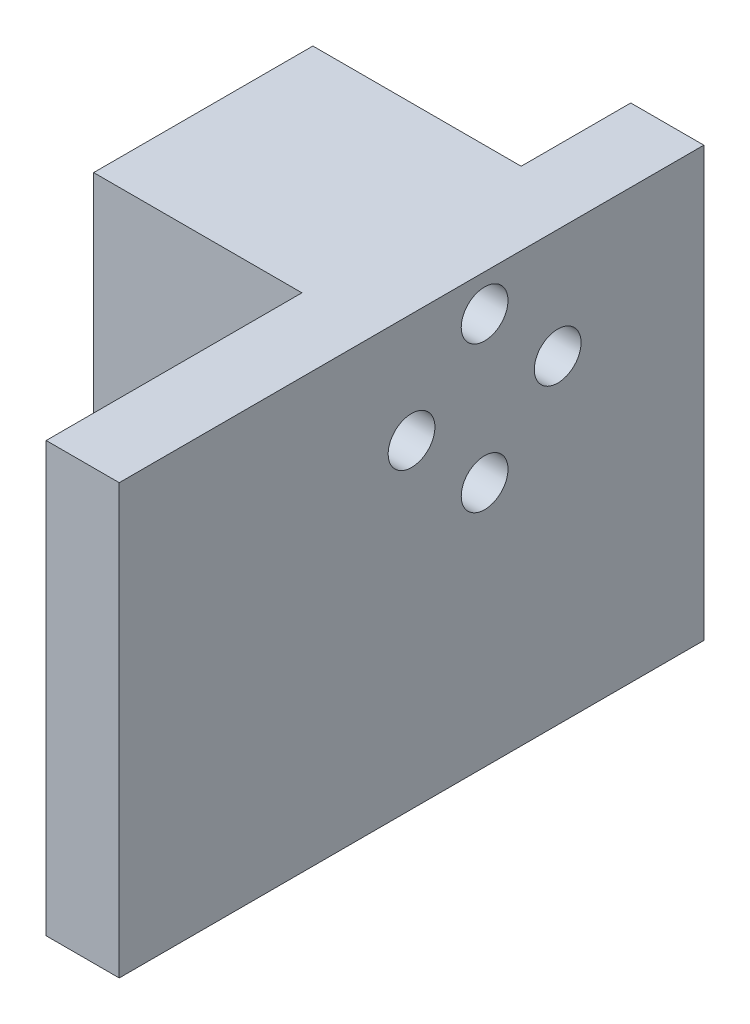
SolidWorks part; units mm, degrees
ref_plane "Front Plane" through (0, 0, 0) normal (0, 0, 1) x (1, 0, 0)
ref_plane "Top Plane" through (0, 0, 0) normal (0, 1, 0) x (1, 0, 0)
ref_plane "Right Plane" through (0, 0, 0) normal (1, 0, 0) x (0, 0, -1)
sketch "Sketch1" plane through (0, 0, 0) normal (0, 1, 0) x (1, 0, 0)
  line L1 (-75, 85) -> (75, 85)
  line L2 (-75, 85) -> (-75, -85)
  line L3 (-75, -85) -> (75, -85)
  line L4 (75, 85) -> (75, -85)
  line L5 (-75, 85) -> (75, -85) construction
  line L6 (-75, -85) -> (75, 85) construction
  line L7 (45, -85) -> (-45, -85)
  line L8 (45, -85) -> (45, -80)
  line L9 (45, -80) -> (-45, -80)
  line L10 (-45, -85) -> (-45, -80)
  line L11 (-18.5, 10) -> (18.5, 10)
  line L12 (-18.5, 10) -> (-18.5, -10)
  line L13 (-18.5, -10) -> (18.5, -10)
  line L14 (18.5, 10) -> (18.5, -10)
  line L15 (-18.5, 10) -> (18.5, -10) construction
  line L16 (-18.5, -10) -> (18.5, 10) construction
  line L17 (45, -85) -> (75, -85)
  line L18 (45, -85) -> (45, -45)
  line L19 (45, -45) -> (75, -45)
  line L20 (75, -85) -> (75, -45)
  line L21 (-45, -85) -> (-75, -85)
  line L22 (-45, -85) -> (-45, -45)
  line L23 (-45, -45) -> (-75, -45)
  line L24 (-75, -85) -> (-75, -45)
  line L25 (75, -25) -> (75, -45)
  line L26 (-7.5, 10) -> (7.5, 10)
  line L27 (45, -45) -> (75, -25)
  line L28 (-45, -45) -> (-75, -25)
  line L29 (-7.5, 10) -> (-7.5, 50)
  line L30 (-7.5, 50) -> (7.5, 50)
  line L31 (7.5, 10) -> (7.5, 50)
  point P0 (0, 0)
  point P10 (0, 0)
  dimension "D1" = 150
  dimension "D2" = 170
  dimension "D3" = 30
  dimension "D4" = 30
  dimension "D5" = 5
  dimension "D6" = 37
  dimension "D7" = 20
  dimension "D8" = 40
  dimension "D9" = 40
  dimension "D10" = 20
  dimension "D11" = 20
  dimension "D12" = 7.5
  dimension "D13" = 7.5
  dimension "D14" = 40
extrude "Boss-Extrude1" add sketch "Sketch1" along normal blind 5 contours L23 L22 L9 L18 L19 L4 L1 L2 L11 L14 L13 L12 region at (0, 0, -82.7701)
sketch "Sketch2" plane through (0, 5, 0) normal (0, 1, 0) x (1, 0, 0)
  line L0 (0, 0) -> (0, -39.6646) construction
sketch "Sketch3" plane through (0, 5, 0) normal (0, 1, 0) x (1, 0, 0)
  line L0 (-18.5, 10) -> (-18.5, -10) construction
  line L1 (-18.5, 10) -> (-7.5, 10) construction
  line L2 (0, 0) -> (0, -17.2633) construction
  circle A0 centre (-35, 20) radius 1.6
  circle A1 centre (-35, -20) radius 1.6
  circle A2 centre (35, -20) radius 1.6
  circle A3 centre (35, 20) radius 1.6
  dimension "D1" = 3.2
  dimension "D2" = 40
  dimension "D3" = 16.5
  dimension "D4" = 10
extrude "Cut-Extrude1" cut sketch "Sketch3" against normal through all and the other way through all
sketch "Sketch4" plane through (0, 5, 0) normal (0, 1, 0) x (1, 0, 0)
  line L0 (-75, 85) -> (75, 85) construction
  line L1 (-75, 85) -> (-70, 85)
  line L2 (-75, 85) -> (-75, -23)
  line L3 (-75, -23) -> (-70, -23)
  line L4 (-70, 85) -> (-70, -23)
  line L5 (-70, -11.5) -> (-75, -11.5)
  line L6 (-70, -11.5) -> (-70, 3.5)
  line L7 (-70, 3.5) -> (-75, 3.5)
  line L8 (-75, -11.5) -> (-75, 3.5)
  line L9 (-70, 23.5) -> (-75, 23.5)
  line L10 (-70, 23.5) -> (-70, 38.5)
  line L11 (-70, 38.5) -> (-75, 38.5)
  line L12 (-75, 23.5) -> (-75, 38.5)
  line L13 (0, 0) -> (0, 26.7337) construction
  line L14 (-70, 3.5) -> (-60, 3.5)
  line L15 (-70, 58.5) -> (-75, 58.5)
  line L16 (-70, 58.5) -> (-70, 73.5)
  line L17 (-70, 73.5) -> (-75, 73.5)
  line L18 (-75, 58.5) -> (-75, 73.5)
  line L19 (-70, 73.5) -> (-60, 73.5)
  line L20 (-70, 73.5) -> (-70, 58.5)
  line L21 (-70, 58.5) -> (-60, 58.5)
  line L22 (-60, 73.5) -> (-60, 58.5)
  line L23 (-70, 3.5) -> (-70, -11.5)
  line L24 (-70, -11.5) -> (-60, -11.5)
  line L25 (-60, 3.5) -> (-60, -11.5)
  circle A0 centre (-65, 66) radius 2.55
  circle A1 centre (-65, -4) radius 2.55
  circle A2 centre (65, 66) radius 2.55
  circle A3 centre (65, -4) radius 2.55
  dimension "D10" = 5.1
  dimension "D12" = 5.1
  dimension "D13" = 7.5
  dimension "D14" = 5
  dimension "D15" = 5
  dimension "D16" = 7.5
  dimension "D1" = 5
  dimension "D2" = 15
  dimension "D3" = 108
  dimension "D4" = 15
  dimension "D5" = 20
  dimension "D6" = 15
  dimension "D7" = 20
  dimension "D8" = 11.5
  dimension "D9" = 10
  dimension "D11" = 10
extrude "Cut-Extrude2" cut sketch "Sketch4" against normal blind 10 contours A0 | A3 | A1 | A2 region at (-65, 5, -66) region at (65, 5, 4)
sketch "Sketch5" plane through (0, 5, 0) normal (0, 1, 0) x (1, 0, 0)
  line L0 (0, 0) -> (0, -51.3371) construction
  line L1 (45, -80) -> (-45, -80) construction
  line L4 (-45, -45) -> (-42, -45)
  line L5 (-45, -45) -> (-45, -80)
  line L6 (-45, -80) -> (-42, -80)
  line L7 (-42, -45) -> (-42, -80)
  line L8 (-42, -70) -> (-36, -70)
  line L9 (-42, -70) -> (-42, -80)
  line L10 (-42, -80) -> (-36, -80)
  line L11 (-36, -70) -> (-36, -80)
  circle A0 centre (-39, -75) radius 1.55
  circle A1 centre (39, -75) radius 1.55
  circle A2 centre (-39, -50) radius 1.55
  circle A3 centre (39, -50) radius 1.55
  dimension "D1" = 3.1
  dimension "D2" = 5
  dimension "D3" = 3
  dimension "D8" = 3.1
  dimension "D9" = 25
  dimension "D10" = 5
  dimension "D4" = 3
  dimension "D5" = 6
  dimension "D6" = 0
  dimension "D7" = 10
extrude "Cut-Extrude3" cut sketch "Sketch5" against normal through all contours A2 | A0 | A1 | A3
sketch "Sketch6" plane through (0, 5, 0) normal (0, 1, 0) x (1, 0, 0)
  line L0 (-75, 85) -> (75, 85) construction
  line L1 (70, 85) -> (55, 85)
  line L2 (70, 85) -> (70, 75)
  line L3 (70, 75) -> (55, 75)
  line L4 (55, 85) -> (55, 75)
  line L5 (75, 85) -> (75, -25) construction
  line L6 (0, 0) -> (0, 22.1653) construction
  line L7 (-55, 85) -> (-55, 75)
  line L8 (-70, 75) -> (-55, 75)
  line L9 (-70, 85) -> (-70, 75)
  line L10 (-70, 85) -> (-55, 85)
  circle A0 centre (62.5, 80) radius 1.55
  circle A1 centre (-62.5, 80) radius 1.55
  dimension "D4" = 3.1
  dimension "D5" = 5
  dimension "D6" = 7.5
  dimension "D1" = 5
  dimension "D2" = 10
  dimension "D3" = 15
extrude "Cut-Extrude4" cut sketch "Sketch6" against normal through all contours A0 | A1 region at (62.5, 5, -80)
sketch "Sketch7" plane through (0, 5, 0) normal (0, 1, 0) x (1, 0, 0)
  line L0 (0, 0) -> (0, 72.5289) construction
  line L1 (-75, 85) -> (-98, 85)
  line L2 (-75, 85) -> (-75, -25)
  line L3 (-75, -25) -> (-98, -25)
  line L4 (-98, 85) -> (-98, -25)
  line L5 (98, 85) -> (98, -25)
  line L6 (75, -25) -> (98, -25)
  line L7 (75, 85) -> (75, -25)
  line L8 (75, 85) -> (98, 85)
  dimension "D1" = 23
extrude "Boss-Extrude2" add sketch "Sketch7" against normal blind 5
sketch "Sketch9" plane through (0, 5, 0) normal (0, 1, 0) x (1, 0, 0)
  line L1 (-44.75, 15) -> (-39.75, 15)
  line L2 (-44.75, 15) -> (-44.75, -25)
  line L3 (-44.75, -25) -> (-39.75, -25)
  line L4 (-39.75, 15) -> (-39.75, -25)
  line L8 (0, 0) -> (0, -58.9253) construction
  line L9 (39.75, 15) -> (39.75, -25)
  line L10 (44.75, -25) -> (39.75, -25)
  line L11 (44.75, 15) -> (44.75, -25)
  line L12 (44.75, 15) -> (39.75, 15)
  line L14 (-98, 85) -> (-98, -25) construction
  dimension "D1" = 53.25
  dimension "D2" = 5
  dimension "D3" = 40
extrude "Boss-Extrude4" add sketch "Sketch9" along normal blind 33
sketch "Sketch11" plane through (0, 5, 0) normal (0, 1, 0) x (1, 0, 0)
  line L0 (-98, 85) -> (-98, -25) construction
  line L1 (-73, 24.3058) -> (-61, 24.3058)
  line L2 (-73, 24.3058) -> (-73, 12.3058)
  line L3 (-73, 12.3058) -> (-61, 12.3058)
  line L4 (-61, 24.3058) -> (-61, 12.3058)
  line L5 (0, 0) -> (0, 34.4815) construction
  line L6 (61, 24.3058) -> (61, 12.3058)
  line L7 (73, 12.3058) -> (61, 12.3058)
  line L8 (73, 24.3058) -> (73, 12.3058)
  line L9 (73, 24.3058) -> (61, 24.3058)
  dimension "D1" = 25
  dimension "D2" = 12
  dimension "D3" = 12
extrude "Cut-Extrude5" cut sketch "Sketch11" against normal blind 50
sketch "Sketch12" plane through (-44.75, 0, 0) normal (-1, 0, 0) x (0, 0, 1)
  line L0 (-15, 38) -> (-15, 5) construction
  line L1 (-7.5, 34.35) -> (7.5, 34.35)
  line L2 (-7.5, 34.35) -> (-7.5, 19.35)
  line L3 (-7.5, 19.35) -> (7.5, 19.35)
  line L4 (7.5, 34.35) -> (7.5, 19.35)
  line L5 (-15, 38) -> (25, 38) construction
  line L6 (0, 34.35) -> (0, 19.35) construction
  line L7 (0, 34.35) -> (0, 26.85) construction
  line L8 (0, 34.35) -> (0, 19.35) construction
  line L9 (0, 19.35) -> (0, 26.85) construction
  line L10 (0, 26.85) -> (7.5, 26.85) construction
  circle A0 centre (0, 31.85) radius 1.6
  circle A4 centre (5, 26.85) radius 1.6
  circle A5 centre (0, 21.85) radius 1.6
  circle A6 centre (-5, 26.85) radius 1.6
  point P23 (-2.6824, 31.0425)
  point P24 (0, 26.85)
  dimension "D5" = 3.2
  dimension "D6" = 5
  dimension "D8" = 0
  dimension "D9" = 5
  dimension "D10" = 5
  dimension "D1" = 7.5
  dimension "D2" = 15
  dimension "D3" = 3.65
  dimension "D4" = 15
  dimension "D7" = 4
extrude "Cut-Extrude6" cut sketch "Sketch12" against normal blind 50 contours A0 | A4 | A6 | A5 region at (-44.75, 31.85, 0) region at (-44.75, 26.85, 5) region at (-44.75, 21.85, 0) region at (-44.75, 26.85, -5)
sketch "Sketch13" plane through (-44.75, 0, 0) normal (-1, 0, 0) x (0, 0, 1)
  line L6 (0, 34.35) -> (0, 19.35) construction
  line L7 (0, 19.35) -> (0, 26.85) construction
  line L8 (0, 26.85) -> (7.5, 26.85) construction
  line L9 (-15, 38) -> (-15, 5) construction
  line L10 (-7.5, 34.35) -> (7.5, 34.35)
  line L11 (-7.5, 34.35) -> (-7.5, 19.35)
  line L12 (-7.5, 19.35) -> (7.5, 19.35)
  line L13 (7.5, 34.35) -> (7.5, 19.35)
  line L14 (-7.5, 34.35) -> (7.5, 19.35) construction
  line L15 (-7.5, 19.35) -> (7.5, 34.35) construction
  circle A2 centre (0, 31.85) radius 1.6
  circle A3 centre (5, 26.85) radius 1.6
  circle A5 centre (-5, 26.85) radius 1.6
  circle A6 centre (0, 21.85) radius 1.6
  dimension "D3" = 5
  dimension "D1" = 7.5
  dimension "D2" = 15
extrude "Boss-Extrude5" add sketch "Sketch13" along normal blind 14.25
ref_plane "Plane2" through (0, 0, 0) normal (-1, 0, 0) x (0, 0, 1)
mirror "Mirror2" about plane through (0, 0, 0) normal (-1, 0, 0) of "Cut-Extrude6"
mirror "Mirror3" about plane through (0, 0, 0) normal (-1, 0, 0) of "Boss-Extrude5"
sketch "Sketch15" plane through (0, 0, 25) normal (0, 0, 1) x (1, 0, 0)
  line L0 (44.75, 19.35) -> (44.75, 34.35) construction
  line L1 (-44.75, 38) -> (44.75, 38)
  line L2 (-44.75, 38) -> (-44.75, 34.35)
  line L3 (-44.75, 34.35) -> (44.75, 34.35)
  line L4 (44.75, 38) -> (44.75, 34.35)
  line L5 (59, 34.35) -> (44.75, 34.35) construction
extrude "Cut-Extrude9" cut sketch "Sketch15" against normal through all
sketch "Sketch18" plane through (0, 5, 0) normal (0, 1, 0) x (1, 0, 0)
  line L0 (-98, -25) -> (-75, -25) construction
  line L1 (-98, 85) -> (-85, 85)
  line L2 (-98, 85) -> (-98, -25)
  line L3 (-98, -25) -> (-85, -25)
  line L4 (-85, 85) -> (-85, -25)
  line L5 (0, 28.0113) -> (0, -28.0113) construction
  line L6 (85, 85) -> (85, -25)
  line L7 (98, -25) -> (85, -25)
  line L8 (98, 85) -> (98, -25)
  line L9 (98, 85) -> (85, 85)
  dimension "D1" = 13
extrude "Cut-Extrude10" cut sketch "Sketch18" against normal through all
fillet "Fillet5" radius 5 2 edges at (44.75, 19.35, 0) (-44.75, 19.35, 0)
sketch "Sketch19" plane through (0, 5, 0) normal (0, 1, 0) x (1, 0, 0)
  line L0 (59, 0) -> (85, 0) construction
  line L1 (59, -7.5) -> (59, 7.5) construction
  line L2 (85, 85) -> (85, -25) construction
  line L3 (85, 0) -> (85, 13) construction
  line L4 (85, 13) -> (85, 78.55) construction
  line L5 (85, 54.5) -> (5, 54.5) construction
  line L6 (5, 54.5) -> (5, 24.5) construction
  line L7 (5, 24.5) -> (85, 24.5) construction
  line L8 (85, 24.5) -> (85, 54.5) construction
  line L9 (85, 54.5) -> (85, 78.5) construction
  circle A0 centre (55, 34.5) radius 1.55
  circle A1 centre (25, 34.5) radius 1.55
  circle A2 centre (25, 44.5) radius 1.55
  circle A3 centre (55, 44.5) radius 1.55
  dimension "D7" = 10
  dimension "3.1" = 3.1
  dimension "D8" = 30
  dimension "D11" = 30
  dimension "D12" = 10
  dimension "D1" = 13
  dimension "D2" = 65.55
  dimension "D3" = 41.5
  dimension "D4" = 80
  dimension "D5" = 30
  dimension "D6" = 24
  dimension "D9" = 2
  dimension "D10" = 2
extrude "Cut-Extrude11" cut sketch "Sketch19" against normal blind 5
mirror "Mirror4" about plane through (0, 0, 0) normal (-1, 0, 0) of "Cut-Extrude11"
sketch "Sketch21" plane through (0, 0, 80) normal (0, 0, 1) x (1, 0, 0)
  line L1 (-85, 0) -> (85, 0)
  line L2 (-85, 0) -> (-85, 5)
  line L3 (-85, 5) -> (85, 5)
  line L4 (85, 0) -> (85, 5)
  line L5 (59, 34.35) -> (39.75, 34.35)
  line L6 (59, 34.35) -> (59, 5)
  line L7 (59, 5) -> (39.75, 5)
  line L8 (39.75, 34.35) -> (39.75, 5)
  line M1 (-45, 0) -> (45, 0)
  line M2 (45, 0) -> (45, 5)
  line M3 (45, 5) -> (-45, 5)
  line M4 (-45, 5) -> (-45, 0)
extrude "Cut-Extrude12" cut sketch "Sketch21" against normal through all contours L3 M4 M1 M2 M3 | L5 L8 L3 L6 M3 | L1 L4 L3 M2 | L3 L4 L1 L2 region at (0, 2.5, 80) region at (65, 2.5, 80) region at (49.375, 19.675, 80)
